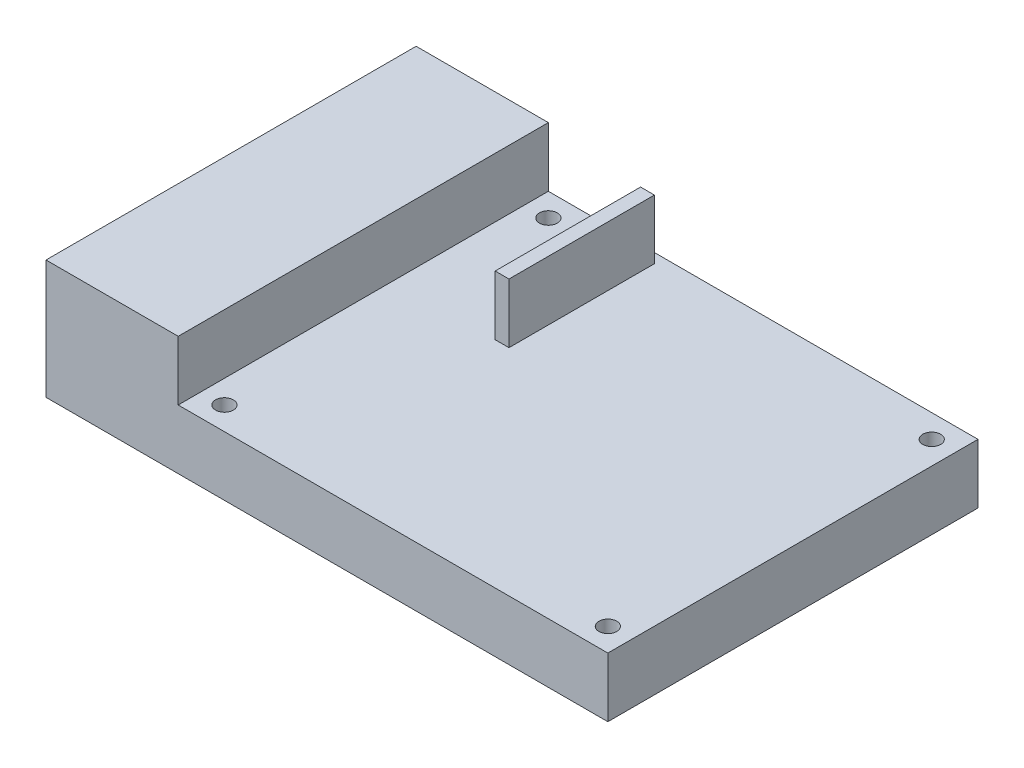
SolidWorks part; units mm, degrees
ref_plane "Front Plane" through (0, 0, 0) normal (0, 0, 1) x (1, 0, 0)
ref_plane "Top Plane" through (0, 0, 0) normal (0, 1, 0) x (1, 0, 0)
ref_plane "Right Plane" through (0, 0, 0) normal (1, 0, 0) x (0, 0, -1)
sketch "Sketch1" plane through (0, 0, 0) normal (0, 1, 0) x (1, 0, 0)
  line L0 (0, 0) -> (0, -56)
  line L1 (0, -56) -> (85, -56)
  line L2 (85, -56) -> (85, 0)
  line L3 (85, 0) -> (0, 0)
  line L4 (20, 0) -> (20, -56)
  line L5 (35.42, -1.4695) -> (35.42, -23.4695)
  line L6 (35.42, -23.4695) -> (37.5134, -23.4695)
  line L7 (37.5134, -23.4695) -> (37.5134, -1.4695)
  line L8 (37.5134, -1.4695) -> (35.42, -1.4695)
  circle A0 centre (23.5, -3.5) radius 1.35
  circle A1 centre (23.5, -52.5) radius 1.35
  circle A2 centre (81.5, -52.5) radius 1.35
  circle A3 centre (81.5, -3.5) radius 1.35
  point P29 (0, -28)
  dimension "D1" = 2.7
  dimension "D2" = 58
  dimension "D3" = 49
  dimension "D4" = 22
  dimension "D5" = 85
  dimension "D6" = 56
  dimension "D7" = 46.08
  dimension "D8" = 3.5
  dimension "D9" = 20
  dimension "D10" = 3.5
extrude "Boss-Extrude1" add sketch "Sketch1" along normal blind 18 contours L4 L3 L0 L1 | L8 L5 L6 L7 region at (10, 0, 28)
extrude "Boss-Extrude2" add sketch "Sketch1<3>" along normal blind 9 contours L3 L4 L1 L2 A3 A2 A1 A0 L8 L7 L6 L5 region at (52.7068, 0, 28.2003)
sketch "Sketch1<3>" plane through (0, 0, 0) normal (0, 1, 0) x (1, 0, 0) same geometry as "Sketch1"
